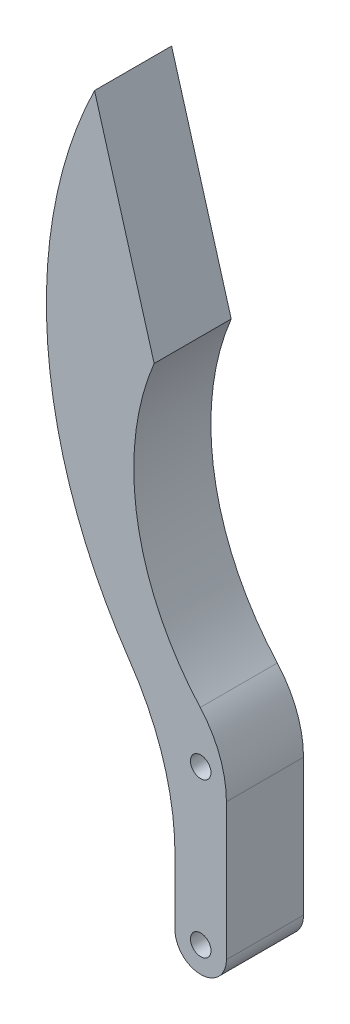
SolidWorks part; units mm, degrees
ref_plane "Front Plane" through (0, 0, 0) normal (0, 0, 1) x (1, 0, 0)
ref_plane "Top Plane" through (0, 0, 0) normal (0, 1, 0) x (1, 0, 0)
ref_plane "Right Plane" through (0, 0, 0) normal (1, 0, 0) x (0, 0, -1)
sketch "Sketch1" plane through (0, 0, 0) normal (0, 0, 1) x (1, 0, 0)
  line L0 (5, 0) -> (5, 5)
  line L1 (0, 0) -> (10, 0)
  line L2 (0, 0) -> (0, 25)
  line L4 (10, 0) -> (10, 40)
  line L5 (0, 0) -> (10, 40) construction
  line L6 (2.3529, 30.5882) -> (10, 0) construction
  line L7 (5, 5) -> (5, 35) construction
  line L8 (5, 35) -> (5, 40) construction
  line L15 (0, 35) -> (0, 25)
  line L17 (-8.7116, 89.7703) -> (-14.4648, 104.0299) construction
  line L18 (-4.8823, 98.1834) -> (-8.4207, 113.5352) construction
  line L20 (-8.4207, 113.5352) -> (-4.0628, 98.4373) construction
  line L21 (-12.9965, 129.3883) -> (-4.0628, 98.4373)
  line L22 (-12.9965, 129.3883) -> (-15.6667, 138.6393)
  circle A0 centre (5, 35) radius 2
  circle A1 centre (5, 5) radius 2
  arc A10 (10, 40) -> (-8.7116, 89.7703) centre (51.36, 83.9522) cw construction
  arc A12 (-14.4648, 104.0299) -> (0, 35) centre (41.4082, 79.7073) ccw construction
  arc A13 (10, 40) -> (-4.8823, 98.1834) centre (43.3244, 79.5188) cw construction
  arc A14 (-8.4207, 113.5352) -> (0, 35) centre (40.8443, 79.0985) ccw construction
  arc A15 (-4.0628, 98.4373) -> (10, 40) centre (42.7016, 78.7803) ccw
  arc A16 (-15.6667, 138.6393) -> (0, 35) centre (67.1584, 98.1558) ccw
  point P4 (5, 20)
  dimension "D5" = 4
  dimension "D6" = 4
  dimension "D1" = 10
  dimension "D2" = 40
  dimension "D3" = 5
  dimension "D4" = 5
  dimension "D7" = 30
extrude "Boss-Extrude1" add sketch "Sketch1" along normal blind 15 contours A1 L7 A0 L8 L2 L1 L0 | A1 L0 L1 L4 L8 A0 L7 region at (-9.1558, 71.8033, 0)
fillet "Fillet1" radius 20 1 edges at (10, 40, 7.5)
fillet "Fillet2" radius 5 2 edges at (0, 0, 7.5) (10, 0, 7.5)
fillet "Fillet3" radius 50 1 edges at (0, 35, 7.5)
